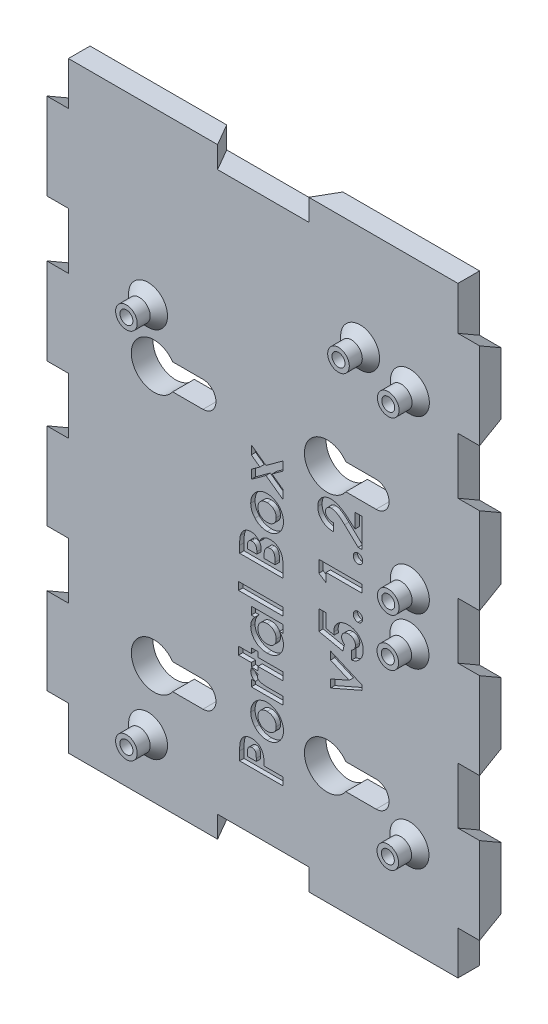
SolidWorks part; units mm, degrees
ref_plane "Front Plane" through (0, 0, 0) normal (1, 0, 0) x (0, 1, 0)
ref_plane "Top Plane" through (0, 0, 0) normal (0, 0, 1) x (0, 1, 0)
ref_plane "Right Plane" through (0, 0, 0) normal (0, 1, 0) x (-1, 0, 0)
sketch "Sketch2" plane through (0, 0, 0) normal (0, 0, 1) x (0, 1, 0)
  line L1 (-60.1282, -37.9423) -> (59.8718, -37.9423) construction
  line L2 (-60.1282, -37.9423) -> (-60.1282, 42.0577) construction
  line L3 (-60.1282, 42.0577) -> (59.8718, 42.0577) construction
  line L4 (59.8718, -37.9423) -> (59.8718, 42.0577) construction
  line L13 (-72.6282, 49.5577) -> (66.3718, 49.5577)
  line L14 (-72.6282, 49.5577) -> (-72.6282, -40.4423)
  line L15 (-72.6282, -40.4423) -> (66.3718, -40.4423)
  line L16 (66.3718, 49.5577) -> (66.3718, -40.4423)
  point P0 (0, 0)
  point P6 (0, 0)
  dimension "D1" = 120
  dimension "D2" = 80
  dimension "D3" = 12.5
  dimension "D5" = 139
  dimension "D6" = 90
  dimension "D7" = 7.5
extrude "Boss-Extrude1" add sketch "Sketch2" along normal blind 5
sketch "Sketch9" plane through (0, 0, 5) normal (0, 0, 1) x (1, 0, 0)
  line L0 (0, 9.5784) -> (0, -57.7301) construction
  text T0 "<b>Portal Box</b>\r\n<b> v5.1.2</b>" font "Century Gothic" height 10
  point P3 (0, -57.7301)
  point P4 (0, 9.5784)
extrude "Cut-Extrude4" cut sketch "Sketch9" against normal blind 1
sketch "Sketch13" plane through (0, 66.3718, -60) normal (0, 1, 0) x (1, 0, 0)
  line L0 (-17.9811, -60) -> (8.8657, -60)
  line L1 (8.8657, -60) -> (-4.5577, -83.25)
  line L2 (-4.5577, -83.25) -> (-17.9811, -60)
  line L5 (40.4423, -65) -> (40.4423, -60) construction
  line L6 (-49.5, -60) -> (49.5, -60) construction
  circle A0 centre (-4.5577, -67.75) radius 7.75
  dimension "D1" = 15.5
  dimension "D2" = 0
  dimension "D3" = 45
extrude "Cut-Extrude5" cut sketch "Sketch13" along normal blind 5 from surface contours L1 L2 L0 starting at face at (-4.5577, -72.6282, 2.5)
extrude "Cut-Extrude6" cut sketch "Sketch13<3>" against normal blind 5 contours L1 L2 L0
sketch "Sketch13<3>" plane through (0, 66.3718, -60) normal (0, 1, 0) x (1, 0, 0) same geometry as "Sketch13"
sketch "Sketch11" plane through (0, 0, 5) normal (0, 0, 1) x (1, 0, 0)
  line L0 (-44.5577, 56.3718) -> (35.4423, 56.3718) construction
  line L1 (-44.5577, 56.3718) -> (-44.5577, -63.6282) construction
  line L2 (-44.5577, -63.6282) -> (35.4423, -63.6282) construction
  line L3 (35.4423, 56.3718) -> (35.4423, -63.6282) construction
  line L4 (-44.5577, 56.3718) -> (35.4423, -63.6282) construction
  line L5 (-44.5577, -63.6282) -> (35.4423, 56.3718) construction
  line L7 (-49.5577, -72.6282) -> (-15.0944, -72.6282) construction
  line L8 (-49.5577, 66.3718) -> (-49.5577, -72.6282) construction
  line L9 (40.4423, -72.6282) -> (40.4423, 66.3718) construction
  circle A0 centre (-31.1577, -59.7282) radius 2.5
  circle A1 centre (-31.1577, 26.2718) radius 2.5
  circle A2 centre (17.8423, 42.2718) radius 1.5
  circle A3 centre (17.8423, 42.2718) radius 2.5
  circle A4 centre (-31.1577, 26.2718) radius 1.5
  circle A5 centre (-31.1577, -59.7282) radius 1.5
  circle A6 centre (29.2423, -51.4282) radius 1.5
  circle A7 centre (29.2423, -11.4282) radius 1.5
  circle A8 centre (29.2423, -51.4282) radius 2.5
  circle A9 centre (29.2423, -11.4282) radius 2.5
  circle A10 centre (29.3423, 39.1718) radius 1.5
  circle A11 centre (29.3423, -0.3282) radius 1.5
  circle A12 centre (29.3423, 39.1718) radius 2.5
  circle A13 centre (29.3423, -0.3282) radius 2.5
  point P6 (0, 0)
  dimension "D5" = 3
  dimension "D6" = 5
  dimension "D8" = 5
  dimension "D9" = 3
  dimension "D11" = 5
  dimension "D12" = 3
  dimension "D17" = 3
  dimension "D18" = 3
  dimension "D19" = 5
  dimension "D20" = 5
  dimension "D25" = 3
  dimension "D26" = 3
  dimension "D27" = 5
  dimension "D28" = 5
  dimension "D1" = 80
  dimension "D2" = 120
  dimension "D3" = 14.1
  dimension "D4" = 17.6
  dimension "D7" = 13.4
  dimension "D10" = 3.9
  dimension "D13" = 12.2
  dimension "D14" = 6.2
  dimension "D15" = 52.2
  dimension "D16" = 6.2
  dimension "D21" = 6.1
  dimension "D22" = 6.1
  dimension "D23" = 56.7
  dimension "D24" = 17.2
  dimension "D29" = 13.4
  dimension "D30" = 30.1
  dimension "D31" = 9
  dimension "D32" = 5
  dimension "D33" = 5
extrude "Boss-Extrude4" add sketch "Sketch11" along normal blind 5
chamfer "Chamfer1" distance 2 angle 45 7 edges at (-28.6577, 26.2718, 5) (-28.6577, -59.7282, 5) (31.7423, -51.4282, 5) (31.7423, -11.4282, 5) (31.8423, -0.3282, 5) (31.8423, 39.1718, 5) (20.3423, 42.2718, 5)
sketch "Sketch14" plane through (0, 0, 0) normal (0, 0, -1) x (1, 0, 0)
  line L0 (21.529, 48.2891) -> (14.529, 48.2891)
  line L1 (21.529, 42.2891) -> (14.529, 42.2891)
  line L2 (21.529, -11.7109) -> (14.529, -11.7109)
  line L3 (21.529, -17.7109) -> (14.529, -17.7109)
  line L4 (-18.471, 48.2891) -> (-25.471, 48.2891)
  line L5 (-18.471, 42.2891) -> (-25.471, 42.2891)
  line L6 (-18.471, -11.7109) -> (-25.471, -11.7109)
  line L7 (-18.471, -17.7109) -> (-25.471, -17.7109)
  line L8 (14.529, 42.2891) -> (14.529, 48.2891)
  line L9 (21.529, 48.2891) -> (21.529, 42.2891)
  line L10 (-25.471, 48.2891) -> (-25.471, 42.2891)
  line L11 (-18.471, 48.2891) -> (-18.471, 42.2891)
  line L12 (-25.471, -11.7109) -> (-25.471, -17.7109)
  line L13 (-18.471, -11.7109) -> (-18.471, -17.7109)
  line L14 (14.529, -11.7109) -> (14.529, -17.7109)
  line L15 (21.529, -11.7109) -> (21.529, -17.7109)
  circle A2 centre (21.529, 45.2891) radius 3
  circle A3 centre (21.529, -14.7109) radius 3
  circle A4 centre (10.2206, 45.2891) radius 5.25
  circle A5 centre (10.2206, -14.7109) radius 5.25
  circle A6 centre (-18.471, 45.2891) radius 3
  circle A7 centre (-18.471, -14.7109) radius 3
  circle A8 centre (-29.7794, 45.2891) radius 5.25
  circle A9 centre (-29.7794, -14.7109) radius 5.25
  point P32 (-30.0001, 37.2152)
  point P33 (-29.7794, 45.2891)
  dimension "D1" = 6
  dimension "D2" = 10.5
  dimension "D3" = 10.5
  dimension "D4" = 6
  dimension "D5" = 10.5
  dimension "D6" = 10.5
  dimension "D7" = 7
  dimension "D8" = 7
  dimension "D9" = 7
  dimension "D10" = 7
  dimension "D11" = 7
  dimension "D12" = 7
  dimension "D13" = 7
  dimension "D14" = 7
  dimension "D15" = 40
  dimension "D16" = 60
extrude "Cut-Extrude7" cut sketch "Sketch14" against normal blind 10 contours A5 | L3 L14 L2 L15 | A3 | A9 | L7 L12 L6 L13 | A7 | A8 | L5 L10 L4 L11 | A6 | A4 | L1 L8 L0 L9 | A2
sketch "Sketch16" plane through (40.4423, 0, 0) normal (1, 0, 0) x (0, 1, 0)
  line L3 (-52.6282, -12.3205) -> (-62.6282, 5)
  line L4 (-62.6282, 5) -> (-42.6282, 5)
  line L5 (-42.6282, 5) -> (-52.6282, -12.3205)
  line L7 (-9.6282, 5) -> (-19.6282, -12.3205)
  line L8 (-19.6282, -12.3205) -> (-29.6282, 5)
  line L9 (-29.6282, 5) -> (-9.6282, 5)
  line L10 (23.3718, 5) -> (13.3718, -12.3205)
  line L11 (13.3718, -12.3205) -> (3.3718, 5)
  line L12 (3.3718, 5) -> (23.3718, 5)
  line L13 (56.3718, 5) -> (46.3718, -12.3205)
  line L14 (46.3718, -12.3205) -> (36.3718, 5)
  line L15 (36.3718, 5) -> (56.3718, 5)
  line L16 (-72.6282, 5) -> (-72.6282, 0) construction
  line L17 (66.3718, 5) -> (66.3718, 0) construction
  line L18 (-72.6282, 5) -> (66.3718, 5) construction
  circle A0 centre (-52.6282, -0.7735) radius 5.7735
  circle A1 centre (-19.6282, -0.7735) radius 5.7735
  circle A2 centre (13.3718, -0.7735) radius 5.7735
  circle A3 centre (46.3718, -0.7735) radius 5.7735
  line M17 (-72.6282, 0) -> (66.3718, 0)
  line M19 (66.3718, 5) -> (-72.6282, 5)
  dimension "D1" = 20
  dimension "D3" = 10
  dimension "D4" = 10
  dimension "D2" = 4
extrude "Boss-Extrude5" add sketch "Sketch16" along normal blind 5 contours A0 M17 | A0 L4 L3 M17 | A0 L5 M17 M19 | A1 L9 L8 M17 | A1 M17 | A1 L7 M17 M19 | A2 M17 | A2 L12 L11 M17 | A3 M17 | A3 L15 L14 M17 | A3 L13 M17 M19 | A2 L10 M17 M19 region at (40.4423, -58.9657, 3.1986) region at (40.4423, -52.6282, 2.0998) region at (40.4423, -46.2907, 3.1986) region at (40.4423, -25.9657, 3.1986) region at (40.4423, -19.6282, 2.0998) region at (40.4423, -13.2907, 3.1986) region at (40.4423, 7.0343, 3.1986) region at (40.4423, 19.7093, 3.1986) region at (40.4423, 13.3718, 2.0998) region at (40.4423, 40.0343, 3.1986) region at (40.4423, 52.7093, 3.1986) region at (40.4423, 46.3718, 2.0998)
extrude "Boss-Extrude6" add sketch "Sketch16<4>" against normal blind 5 from surface contours A0 L4 L3 M17 | A0 M17 | A0 L5 M17 M19 | A1 M17 | A1 L9 L8 M17 | A1 L7 M17 M19 | A2 L12 L11 M17 | A2 M17 | A2 L10 M17 M19 | A3 L15 L14 M17 | A3 M17 | A3 L13 M17 M19 region at (40.4423, -58.9657, 3.1986) region at (40.4423, -52.6282, 2.0998) region at (40.4423, -46.2907, 3.1986) region at (40.4423, -25.9657, 3.1986) region at (40.4423, -19.6282, 2.0998) region at (40.4423, -13.2907, 3.1986) region at (40.4423, 7.0343, 3.1986) region at (40.4423, 19.7093, 3.1986) region at (40.4423, 13.3718, 2.0998) region at (40.4423, 40.0343, 3.1986) region at (40.4423, 52.7093, 3.1986) region at (40.4423, 46.3718, 2.0998) starting at face at (-49.5577, -3.1282, 2.5)
sketch "Sketch16<4>" plane through (40.4423, 0, 0) normal (1, 0, 0) x (0, 1, 0) same geometry as "Sketch16"
